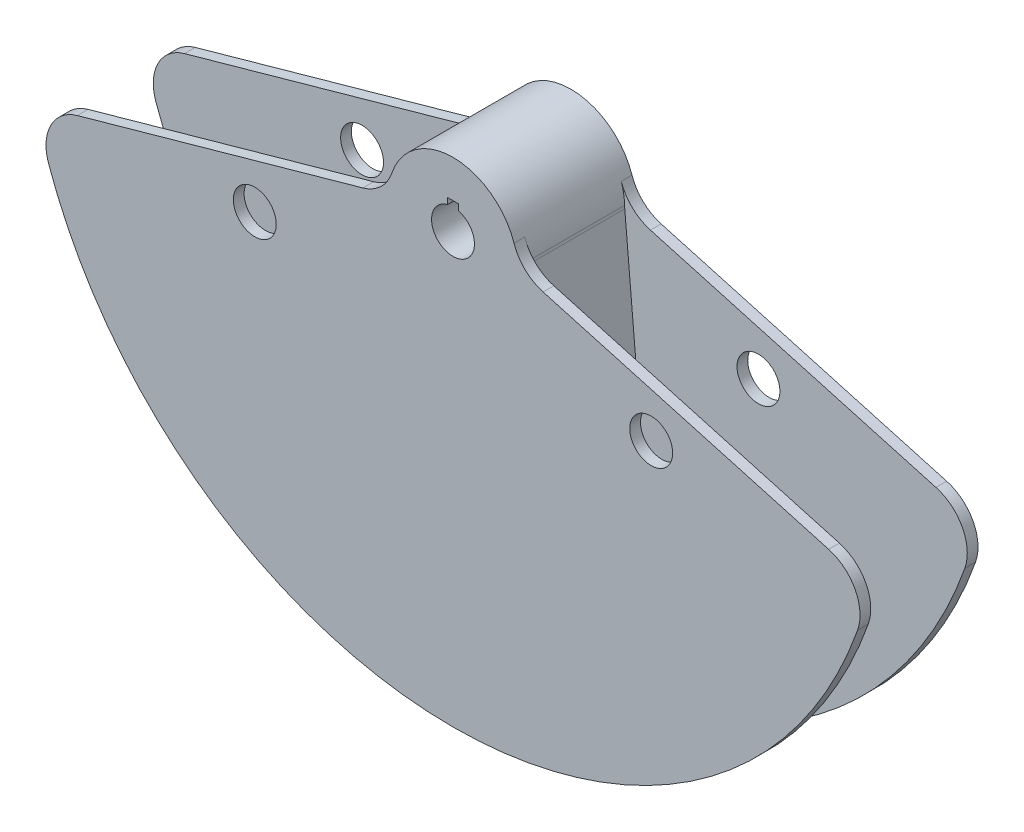
SolidWorks part; units mm, degrees
material "AISI 1020"
ref_plane "Front Plane" through (0, 0, 0) normal (0, 0, 1) x (1, 0, 0)
ref_plane "Top Plane" through (0, 0, 0) normal (0, 1, 0) x (1, 0, 0)
ref_plane "Right Plane" through (0, 0, 0) normal (1, 0, 0) x (0, 0, -1)
other "Center of Mass"
sketch "Sketch1" plane through (0, 0, 0) normal (0, 0, 1) x (1, 0, 0)
  line L0 (-59.6996, -246.8845) -> (-38.1844, -0.9642)
  line L1 (-38.1, 0) -> (38.1, 0) construction
  line L2 (38.1844, -0.9642) -> (59.6996, -246.8845)
  line L3 (0, 0) -> (-117.3327, -48.6008) construction
  line L4 (0, 0) -> (0, -254) construction
  line L5 (117.3327, -48.6008) -> (0, 0) construction
  arc A0 (-59.6996, -246.8845) -> (59.6996, -246.8845) centre (0, 0) ccw
  circle A1 centre (0, 0) radius 127 construction
  circle A2 centre (0, 0) radius 12.7
  arc A3 (38.0926, 0.7497) -> (-38.0926, 0.7497) centre (0, 0) ccw
  circle A4 centre (-117.3327, -48.6008) radius 12.7 construction
  circle A5 centre (117.3327, -48.6008) radius 12.7 construction
  arc A6 (38.1844, -0.9642) -> (38.0926, 0.7497) centre (63.4877, 1.2495) cw
  arc A7 (-38.1844, -0.9642) -> (-38.0926, 0.7497) centre (-63.4877, 1.2495) ccw
  dimension "D1" = 508
  dimension "D2" = 254
  dimension "D3" = 25.4
  dimension "D4" = 25.4
  dimension "D5" = 25.4
  dimension "D8" = 25.4
  dimension "D6" = 135
  dimension "D7" = 67.5
  dimension "D9" = 10
extrude "Boss-Extrude1" add sketch "Sketch1" along normal mid plane 57.15
sketch "Sketch5" plane through (0, 0, 28.575) normal (0, 0, 1) x (1, 0, 0)
  line L0 (-222.4045, -51.6882) -> (-53.3494, -4.2767)
  line L1 (-38.1, 0) -> (38.1, 0) construction
  line L2 (53.3494, -4.2767) -> (222.4045, -51.6882)
  line L3 (0, 0) -> (-117.3327, -48.6008) construction
  line L4 (0, 0) -> (0, -254) construction
  line L5 (117.3327, -48.6008) -> (0, 0) construction
  arc A0 (-239.4952, -84.6052) -> (239.4952, -84.6052) centre (0, 0) ccw
  circle A1 centre (0, 0) radius 127 construction
  circle A2 centre (0, 0) radius 12.7
  arc A3 (36.1249, 12.1078) -> (-36.1249, 12.1078) centre (0, 0) ccw
  circle A4 centre (-117.3327, -48.6008) radius 12.7
  circle A5 centre (117.3327, -48.6008) radius 12.7
  arc A6 (53.3494, -4.2767) -> (36.1249, 12.1078) centre (60.2082, 20.1797) cw
  arc A7 (-53.3494, -4.2767) -> (-36.1249, 12.1078) centre (-60.2082, 20.1797) ccw
  arc A8 (-222.4045, -51.6882) -> (-239.4952, -84.6052) centre (-215.5457, -76.1446) ccw
  arc A9 (222.4045, -51.6882) -> (239.4952, -84.6052) centre (215.5457, -76.1446) cw
  dimension "D1" = 508
  dimension "D2" = 254
  dimension "D3" = 25.4
  dimension "D5" = 25.4
  dimension "D8" = 25.4
  dimension "D4" = 25.4
  dimension "D10" = 25.4
  dimension "D6" = 135
  dimension "D7" = 67.5
  dimension "D9" = 25.4
extrude "Boss-Extrude2" add sketch "Sketch5" along normal blind 6.35
sketch "Sketch6" plane through (0, 0, -28.575) normal (0, 0, -1) x (-1, 0, 0)
  line L0 (-222.4045, -51.6882) -> (-53.3494, -4.2767)
  line L1 (-38.1, 0) -> (38.1, 0) construction
  line L2 (53.3494, -4.2767) -> (222.4045, -51.6882)
  line L3 (0, 0) -> (-117.3327, -48.6008) construction
  line L4 (0, 0) -> (0, -254) construction
  line L5 (117.3327, -48.6008) -> (0, 0) construction
  arc A0 (-239.4952, -84.6052) -> (239.4952, -84.6052) centre (0, 0) ccw
  circle A1 centre (0, 0) radius 127 construction
  circle A2 centre (0, 0) radius 12.7
  arc A3 (36.1249, 12.1078) -> (-36.1249, 12.1078) centre (0, 0) ccw
  circle A4 centre (-117.3327, -48.6008) radius 12.7
  circle A5 centre (117.3327, -48.6008) radius 12.7
  arc A6 (53.3494, -4.2767) -> (36.1249, 12.1078) centre (60.2082, 20.1797) cw
  arc A7 (-53.3494, -4.2767) -> (-36.1249, 12.1078) centre (-60.2082, 20.1797) ccw
  arc A8 (222.4045, -51.6882) -> (239.4952, -84.6052) centre (215.5457, -76.1446) cw
  arc A9 (-222.4045, -51.6882) -> (-239.4952, -84.6052) centre (-215.5457, -76.1446) ccw
  dimension "D1" = 508
  dimension "D2" = 254
  dimension "D3" = 25.4
  dimension "D4" = 25.4
  dimension "D7" = 25.4
  dimension "D9" = 25.4
  dimension "D10" = 25.4
  dimension "D5" = 135
  dimension "D6" = 67.5
  dimension "D8" = 25.4
extrude "Boss-Extrude4" add sketch "Sketch6" along normal blind 6.35
sketch "Sketch8" plane through (0, 0, 0) normal (0, 0, 1) x (1, 0, 0)
  line L0 (0, 0) -> (0, 12.7) construction
  line L2 (3.175, 9.525) -> (-3.175, 9.525)
  line L3 (3.175, 9.525) -> (3.175, 15.875)
  line L4 (3.175, 15.875) -> (-3.175, 15.875)
  line L5 (-3.175, 9.525) -> (-3.175, 15.875)
  line L6 (3.175, 9.525) -> (-3.175, 15.875) construction
  line L7 (3.175, 15.875) -> (-3.175, 9.525) construction
  circle A0 centre (0, 0) radius 12.7 construction
  arc A1 (3.175, 12.2967) -> (-3.175, 12.2967) centre (0, 0) ccw
  dimension "D1" = 6.35
  dimension "D2" = 6.35
extrude "Cut-Extrude1" cut sketch "Sketch8" against normal through all both and the other way through all contours L3 L4 L5 L2
